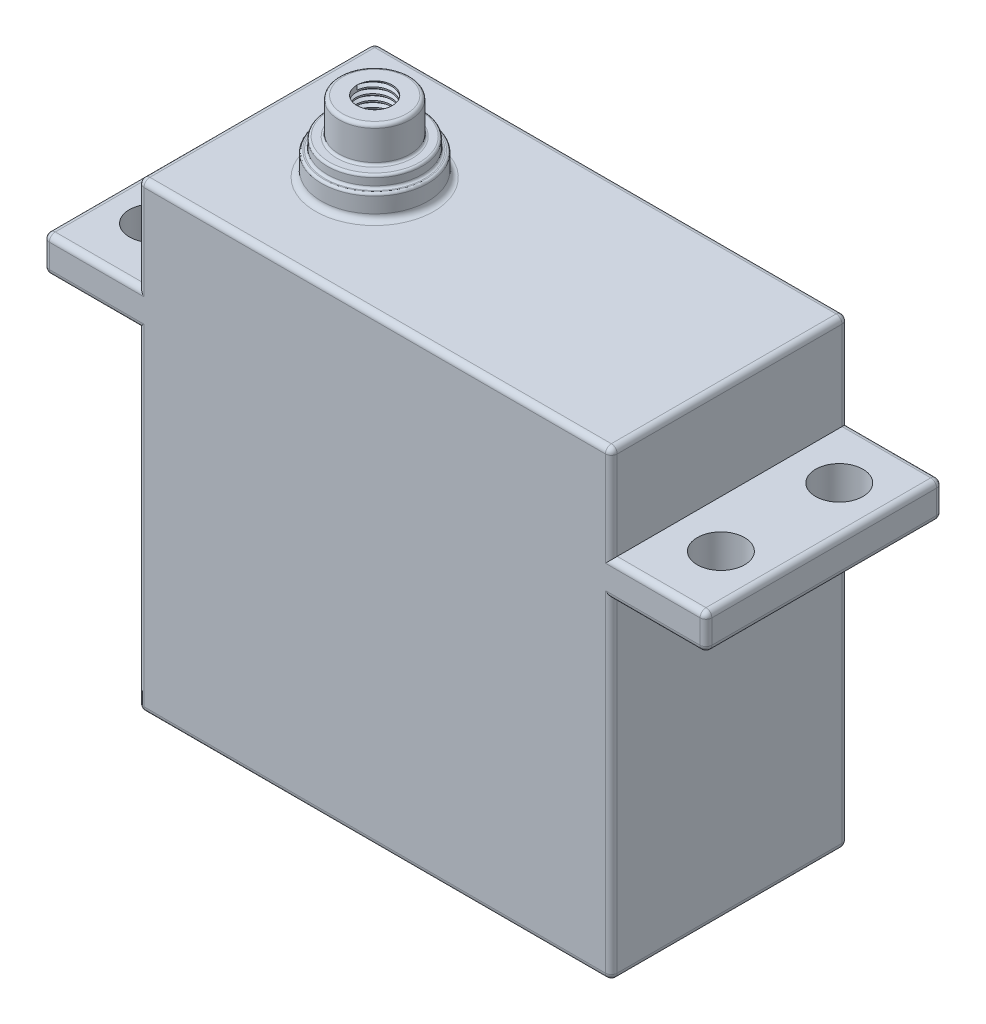
SolidWorks part; units mm, degrees
ref_plane "前视基准面" through (0, 0, 0) normal (0, 0, 1) x (1, 0, 0)
ref_plane "上视基准面" through (0, 0, 0) normal (0, 1, 0) x (1, 0, 0)
ref_plane "右视基准面" through (0, 0, 0) normal (1, 0, 0) x (0, 0, -1)
other "Configuration Table"
sketch "草图1" plane through (0, 0, 0) normal (0, 0, 1) x (1, 0, 0)
  line L1 (0, 0) -> (40, 0)
  line L2 (0, 0) -> (0, 39)
  line L3 (0, 39) -> (40, 39)
  line L4 (40, 0) -> (40, 39)
  dimension "D1" = 40
  dimension "39" = 39
extrude "凸台-拉伸1" add sketch "草图1" along normal blind 20
sketch "草图2" plane through (0, 0, 0) normal (-1, 0, 0) x (0, 0, 1)
  line L0 (0, 39) -> (0, 0) construction
  line L1 (0, 28) -> (20, 28)
  line L2 (0, 28) -> (0, 31)
  line L3 (0, 31) -> (20, 31)
  line L4 (20, 28) -> (20, 31)
  line L5 (20, 39) -> (20, 0) construction
  line L6 (20, 0) -> (0, 0) construction
  dimension "D1" = 31
  dimension "D2" = 3
extrude "凸台-拉伸2" add sketch "草图2" along normal blind 8
sketch "草图3" plane through (40, 0, 0) normal (1, 0, 0) x (0, 0, -1)
  line L12 (0, 28) -> (0, 31)
  line L13 (-20, 28) -> (0, 28)
  line L14 (-20, 31) -> (-20, 28)
  line L15 (0, 31) -> (-20, 31)
  line L16 (0, 28) -> (0, 31)
  line L17 (-20, 28) -> (0, 28)
  line L18 (-20, 31) -> (-20, 28)
  line L19 (0, 31) -> (-20, 31)
  dimension "D2" = 0
extrude "凸台-拉伸3" add sketch "草图3" along normal blind 8 contours L16 L19 L18 L17
sketch "草图4" plane through (0, 31, 0) normal (0, 1, 0) x (1, 0, 0)
  line L1 (0, -20) -> (0, 0) construction
  circle A0 centre (-4, -4.7329) radius 2
  circle A1 centre (-4, -14.736) radius 2
  dimension "D2" = 4
  dimension "D1" = 10.0031
  dimension "D3" = 4
extrude "切除-拉伸1" cut sketch "草图4" against normal up to next and the other way through all
sketch "草图5" plane through (0, 39, 0) normal (0, 1, 0) x (1, 0, 0)
  line L0 (20, 0) -> (20, -20) construction
  line L1 (40, 0) -> (0, 0) construction
  line L2 (40, -20) -> (0, -20) construction
ref_plane "基准面1" through (20, 0, 0) normal (-1, 0, 0) x (0, 0, 1)
mirror "镜向1" about plane through (20, 0, 0) normal (-1, 0, 0) of "切除-拉伸1"
sketch "草图6" plane through (0, 39, 0) normal (0, 1, 0) x (1, 0, 0)
  line L4 (40, 0) -> (0, 0) construction
  circle A0 centre (10, -10) radius 4.5
  dimension "D2" = 9
  dimension "D1" = 14
  dimension "D3" = 10
extrude "凸台-拉伸4" add sketch "草图6" along normal blind 2
sketch "草图7" plane through (0, 41, 0) normal (0, 1, 0) x (1, 0, 0)
  circle A0 centre (10, -10) radius 4
  dimension "D1" = 8
extrude "凸台-拉伸5" add sketch "草图7" along normal blind 1
sketch "草图9" plane through (0, 42, 0) normal (0, 1, 0) x (1, 0, 0)
  circle A1 centre (10, -10) radius 3
  dimension "D1" = 6
extrude "凸台-拉伸6" add sketch "草图9" along normal blind 3
sketch "草图10" plane through (0, 45, 0) normal (0, 1, 0) x (1, 0, 0)
  circle A0 centre (10, -10) radius 1.5
  dimension "D1" = 3
extrude "切除-拉伸3" cut sketch "草图10" against normal blind 3
thread "螺纹线2" pitch 0.5 method cut profile "螺纹线轮廓3" start angle 0, offset 0, length 0, pitch 0.5, diameter 3
ref_plane "基准面4" through (8.5, 45, 10) normal (0, 0, 1) x (-1, 0, 0)
sketch "螺纹线轮廓3" plane through (8.5, 45, 10) normal (0, 0, 1) x (-1, 0, 0)
  line L0 (0, 0) -> (0, 0.5) construction
  line L1 (0, 0) -> (0.2706, 0.1562)
  line L2 (0.2706, 0.1562) -> (0.2706, 0.2187)
  line L3 (0.2706, 0.2187) -> (0, 0.375)
  line L4 (0.2706, 0.1875) -> (0, 0.1875) construction
  line L11 (0, 0) -> (0, 0.375)
  point P2 (0, 0)
  dimension "Pitch" = 0.5
  dimension "Profile_Angle" = 60
  dimension "Profile_Land" = 0.0625
  dimension "Profile_Height" = 0.2706
fillet "圆角1" radius 0.5 4 edges at (0, 0, 10) (20, 0, 20) (40, 0, 10) (20, 0, 0)
fillet "圆角2" radius 0.5 5 edges at (40, 39, 10) (20, 39, 20) (0, 39, 10) (20, 39, 0) (10, 39, 5.5)
fillet "圆角3" radius 0.5 32 edges at (0.1464, 0.1464, 0.1464) (39.8536, 0.1464, 0.1464) (39.8536, 38.8536, 0.1464) (0.1464, 38.8536, 0.1464) (39.8536, 0.1464, 19.8536) (0.1464, 0.1464, 19.8536) (0.1464, 38.8536, 19.8536) (39.8536, 38.8536, 19.8536) (-4, 31, 0) (-8, 29.5, 0) (-4, 28, 0) (0, 14.25, 0) (40, 14.25, 0) (44, 28, 0) (48, 29.5, 0) (44, 31, 0) (40, 34.75, 0) (0, 34.75, 0) (44, 31, 20) (48, 29.5, 20) (44, 28, 20) (40, 14.25, 20) (0, 14.25, 20) (-4, 28, 20) (-8, 29.5, 20) (-4, 31, 20) (0, 34.75, 20) (40, 34.75, 20) (48, 31, 10) (48, 28, 10) (-8, 31, 10) (-8, 28, 10)
fillet "圆角4" radius 0.2 4 edges at (10, 42, 14) (10, 42, 13) (10, 41, 14.5) (10, 41, 14)
fillet "圆角5" radius 0.3 1 edges at (10, 45, 13)
